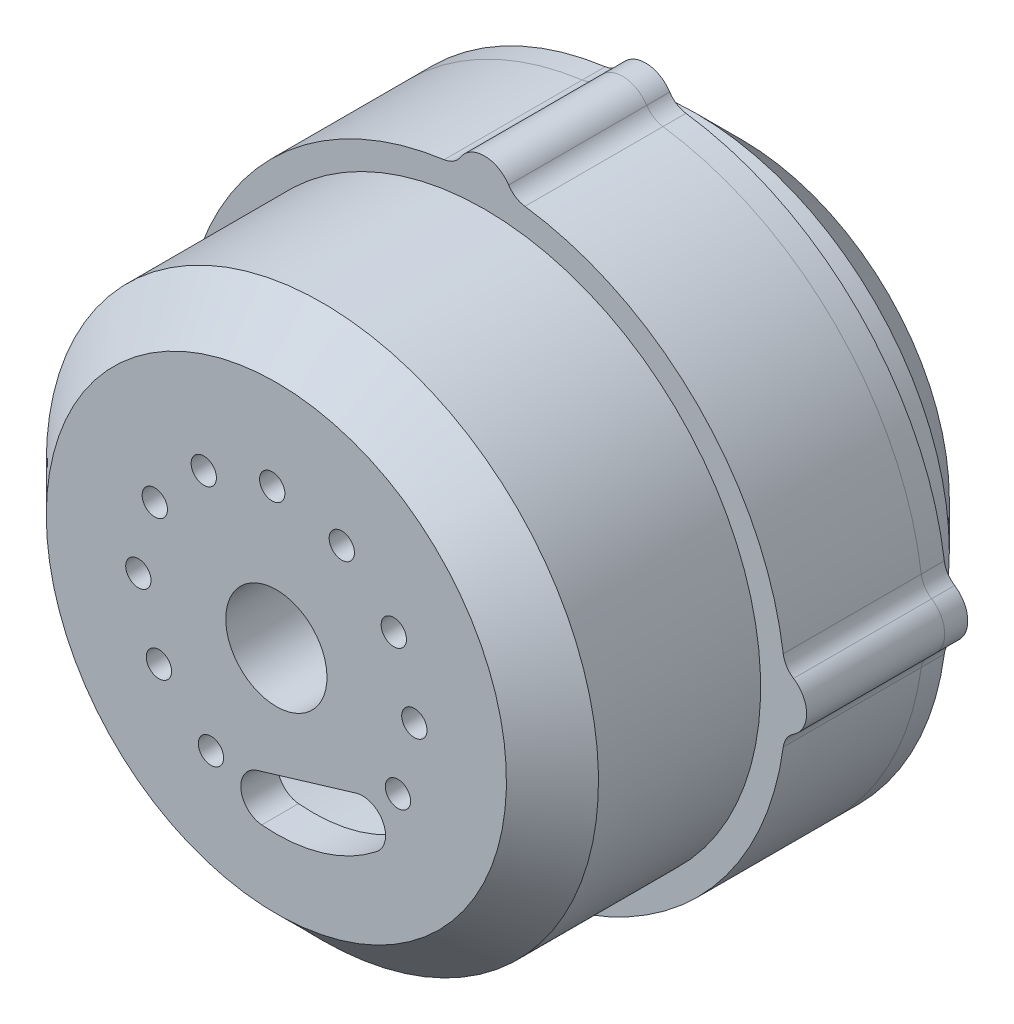
SolidWorks part; units mm, degrees
material "6061-T6 (SS)"
ref_plane "Front Plane" through (0, 0, 0) normal (0, 0, 1) x (1, 0, 0)
ref_plane "Top Plane" through (0, 0, 0) normal (0, 1, 0) x (1, 0, 0)
ref_plane "Right Plane" through (0, 0, 0) normal (1, 0, 0) x (0, 0, -1)
sketch "Sketch3" plane through (0, 0, 0) normal (1, 0, 0) x (0, 0, -1)
  line L0 (7, 57.5) -> (-6, 57.5)
  line L1 (-6, 57.5) -> (-6, 52.5)
  line L2 (-6, 57.5) -> (-6, 46.1394) construction
  line L3 (-6, 52.5) -> (-60.2341, 52.5)
  line L4 (-32.9966, 19) -> (-32.9966, 12)
  line L5 (-32.9966, 12) -> (-38.9966, 12)
  line L6 (-38.9966, 12) -> (-38.9966, 11)
  line L7 (-38.9966, 11) -> (-68.2341, 11)
  line L8 (-68.2341, -47.5) -> (-68.2341, 47.5) construction
  line L9 (-68.2341, 11) -> (-68.2341, 70)
  line L10 (-68.2341, 70) -> (7, 70)
  line L11 (7, 70) -> (7, 57.5)
  line L12 (-68.2341, 0) -> (33.0822, 0) construction
  line L14 (-38.9966, 11.7) -> (-38.9966, -11.7) construction
  line L15 (-33.2966, 12) -> (-38.6966, 12) construction
  line L16 (-32.9966, -11.7) -> (-32.9966, 11.7) construction
  line L21 (-32.9966, 19) -> (-60.2341, 19)
  line L22 (-60.2341, 19) -> (-60.2341, 52.5)
  line L23 (6, 46.1394) -> (6, 57.5) construction
  point P7 (6, 57.5)
  point P19 (7.2365, 57.5)
  point P29 (-60.0808, 52.5)
  dimension "D1" = 5
  dimension "D2" = 140
  dimension "D3" = 1
  dimension "D4" = 1
  dimension "D5" = 8
  dimension "D6" = 8
revolve "Revolve1" add sketch "Sketch3" angle 360 about L12
sketch "Sketch5" plane through (0, 0, -7) normal (0, 0, -1) x (-1, 0, 0)
  arc A16 (38.9134, -45.4201) -> (34.3133, -46.1394) centre (37.297, -50.1516) ccw
  arc A17 (38.9134, -45.4201) -> (45.4201, -38.9134) centre (40.5703, -40.5703) ccw
  arc A18 (46.1394, -34.3133) -> (45.4201, -38.9134) centre (50.1516, -37.297) ccw
  arc A19 (46.1394, -34.3133) -> (46.1394, 34.3133) centre (0, 0) ccw
  arc A20 (45.4201, 38.9134) -> (46.1394, 34.3133) centre (50.1516, 37.297) ccw
  arc A21 (45.4201, 38.9134) -> (38.9134, 45.4201) centre (40.5703, 40.5703) ccw
  arc A22 (34.3133, 46.1394) -> (38.9134, 45.4201) centre (37.297, 50.1516) ccw
  arc A23 (34.3133, 46.1394) -> (-34.3133, 46.1394) centre (0, 0) ccw
  arc A24 (-38.9134, 45.4201) -> (-34.3133, 46.1394) centre (-37.297, 50.1516) ccw
  arc A25 (-38.9134, 45.4201) -> (-45.4201, 38.9134) centre (-40.5703, 40.5703) ccw
  arc A26 (-46.1394, 34.3133) -> (-45.4201, 38.9134) centre (-50.1516, 37.297) ccw
  arc A27 (-46.1394, 34.3133) -> (-46.1394, -34.3133) centre (0, 0) ccw
  arc A28 (-45.4201, -38.9134) -> (-46.1394, -34.3133) centre (-50.1516, -37.297) ccw
  arc A29 (-45.4201, -38.9134) -> (-38.9134, -45.4201) centre (-40.5703, -40.5703) ccw
  arc A30 (-34.3133, -46.1394) -> (-38.9134, -45.4201) centre (-37.297, -50.1516) ccw
  arc A31 (-34.3133, -46.1394) -> (34.3133, -46.1394) centre (0, 0) ccw
  arc A32 (38.9134, -45.4201) -> (34.3133, -46.1394) centre (37.297, -50.1516) ccw
  arc A33 (38.9134, -45.4201) -> (45.4201, -38.9134) centre (40.5703, -40.5703) ccw
  arc A34 (46.1394, -34.3133) -> (45.4201, -38.9134) centre (50.1516, -37.297) ccw
  arc A35 (46.1394, -34.3133) -> (46.1394, 34.3133) centre (0, 0) ccw
  arc A36 (45.4201, 38.9134) -> (46.1394, 34.3133) centre (50.1516, 37.297) ccw
  arc A37 (45.4201, 38.9134) -> (38.9134, 45.4201) centre (40.5703, 40.5703) ccw
  arc A38 (34.3133, 46.1394) -> (38.9134, 45.4201) centre (37.297, 50.1516) ccw
  arc A39 (34.3133, 46.1394) -> (-34.3133, 46.1394) centre (0, 0) ccw
  arc A40 (-38.9134, 45.4201) -> (-34.3133, 46.1394) centre (-37.297, 50.1516) ccw
  arc A41 (-38.9134, 45.4201) -> (-45.4201, 38.9134) centre (-40.5703, 40.5703) ccw
  arc A42 (-46.1394, 34.3133) -> (-45.4201, 38.9134) centre (-50.1516, 37.297) ccw
  arc A43 (-46.1394, 34.3133) -> (-46.1394, -34.3133) centre (0, 0) ccw
  arc A44 (-45.4201, -38.9134) -> (-46.1394, -34.3133) centre (-50.1516, -37.297) ccw
  arc A45 (-45.4201, -38.9134) -> (-38.9134, -45.4201) centre (-40.5703, -40.5703) ccw
  arc A46 (-34.3133, -46.1394) -> (-38.9134, -45.4201) centre (-37.297, -50.1516) ccw
  arc A47 (-34.3133, -46.1394) -> (34.3133, -46.1394) centre (0, 0) ccw
  dimension "D1" = 0
extrude "Cut-Extrude2" cut sketch "Sketch5" against normal up to surface (13 mm away) up to face at (0, -57.5, 6)
sketch "Sketch6" plane through (0, 0, 6) normal (0, 0, -1) x (-1, 0, 0)
  circle A0 centre (-40.5703, 40.5703) radius 2.0193
  circle A1 centre (40.5703, 40.5703) radius 2.0193
  circle A2 centre (40.5703, -40.5703) radius 2.0193
  circle A3 centre (-40.5703, -40.5703) radius 2.0193
  dimension "D1" = 4.0386
extrude "Cut-Extrude3" cut sketch "Sketch6" against normal blind 25
sketch "Sketch4" plane through (0, 0, 68.2341) normal (0, 0, 1) x (1, 0, 0)
  line L0 (-4.1627, -25.0873) -> (17.2952, -18.6434)
  circle A0 centre (26.4181, -14.2156) radius 2.75
  circle A1 centre (29.9866, 0.8979) radius 2.75
  circle A2 centre (25.5202, 15.7709) radius 2.75
  circle A3 centre (14.2156, 26.4181) radius 2.75
  circle A4 centre (-0.8979, 29.9866) radius 2.75
  circle A5 centre (-15.7709, 25.5202) radius 2.75
  circle A6 centre (-26.4181, 14.2156) radius 2.75
  circle A7 centre (-29.9866, -0.8979) radius 2.75
  circle A8 centre (-25.5202, -15.7709) radius 2.75
  circle A9 centre (-14.2156, -26.4181) radius 2.75
  arc A10 (-14.2156, -26.4181) -> (26.4181, -14.2156) centre (0, 0) ccw construction
  arc A11 (-2.7247, -29.876) -> (18.7333, -23.4321) centre (0, 0) ccw construction
  arc A12 (-3.1788, -34.8554) -> (21.8555, -27.3375) centre (0, 0) ccw
  arc A14 (-4.1627, -25.0873) -> (-3.1788, -34.8554) centre (-2.7247, -29.876) ccw
  arc A15 (21.8555, -27.3375) -> (17.2952, -18.6434) centre (18.7333, -23.4321) ccw
  point P34 (8.6284, -28.7324)
  point P37 (21.8555, -27.3375)
  point P38 (18.7335, -23.432)
  dimension "D1" = 5.5
  dimension "D2" = 12
  dimension "D3" = 5
  dimension "D4" = 12.17
extrude "Cut-Extrude1" cut sketch "Sketch4" against normal up to next
sketch "Sketch7" plane through (0, 0, 68.2341) normal (0, 0, 1) x (1, 0, 0)
  circle A2 centre (0, 0) radius 60
  dimension "D1" = 120
extrude "Cut-Extrude4" cut sketch "Sketch7" against normal offset from surface (45.2341 mm away) 30 flip side to cut up to face at (0, 0, -7)
sketch "Sketch8" plane through (0, 0, -7) normal (0, 0, -1) x (-1, 0, 0)
  line L0 (-70, 0) -> (-57.5, 0) construction
  circle A0 centre (-63.75, 0) radius 2.4892
  circle A1 centre (0, 0) radius 70 construction
  arc A2 (-46.1394, 34.3133) -> (-46.1394, -34.3133) centre (0, 0) ccw construction
  circle A3 centre (0, 63.75) radius 2.4892
  circle A4 centre (63.75, 0) radius 2.4892
  circle A5 centre (0, -63.75) radius 2.4892
  arc A8 (-67.1471, 5.2462) -> (-67.1471, -5.2462) centre (-63.75, 0) ccw
  arc A9 (5.2462, 67.1471) -> (-5.2462, 67.1471) centre (0, 63.75) ccw
  arc A10 (67.1471, -5.2462) -> (67.1471, 5.2462) centre (63.75, 0) ccw
  arc A11 (-5.2462, -67.1471) -> (5.2462, -67.1471) centre (0, -63.75) ccw
  arc A12 (-64.9098, -8.7734) -> (-8.7734, -64.9098) centre (0, 0) ccw
  arc A13 (-8.7734, 64.9098) -> (-64.9098, 8.7734) centre (0, 0) ccw
  arc A14 (64.9098, 8.7734) -> (8.7734, 64.9098) centre (0, 0) ccw
  arc A15 (8.7734, -64.9098) -> (64.9098, -8.7734) centre (0, 0) ccw
  arc A16 (-5.2462, -67.1471) -> (-8.7734, -64.9098) centre (-9.4431, -69.8647) ccw
  arc A17 (5.2462, -67.1471) -> (8.7734, -64.9098) centre (9.4431, -69.8647) cw
  arc A18 (67.1471, -5.2462) -> (64.9098, -8.7734) centre (69.8647, -9.4431) ccw
  arc A19 (67.1471, 5.2462) -> (64.9098, 8.7734) centre (69.8647, 9.4431) cw
  arc A20 (5.2462, 67.1471) -> (8.7734, 64.9098) centre (9.4431, 69.8647) ccw
  arc A21 (-5.2462, 67.1471) -> (-8.7734, 64.9098) centre (-9.4431, 69.8647) cw
  arc A22 (-64.9098, -8.7734) -> (-67.1471, -5.2462) centre (-69.8647, -9.4431) ccw
  arc A23 (-67.1471, 5.2462) -> (-64.9098, 8.7734) centre (-69.8647, 9.4431) ccw
  circle A24 centre (0, 0) radius 70
  point P18 (0, 0)
  point P32 (0, 0)
  point P33 (6.0752, -65.2176)
  point P38 (65.2176, 6.0752)
  point P43 (-6.0752, 65.2176)
  point P48 (0, 0)
  circle M37 centre (0, 0) radius 70
  dimension "D1" = 4.9784
  dimension "D3" = 65.5
  dimension "D4" = 4
  dimension "D5" = 5
  dimension "D2" = 4
extrude "Cut-Extrude5" cut sketch "Sketch8" against normal through all contours A8 A23 A13 A21 A9 M37 | A9 A20 A14 A19 A10 M37 | A10 A18 A15 A17 A11 M37 | A12 A22 A8 A11 A16 M37 region at (69.3276, 3.0332, -7) region at (69.3276, -3.0332, -7) region at (-48.7975, 48.7975, -7) region at (-3.0332, -69.3276, -7)
chamfer "Chamfer1" distance 10 angle 45 1 edges at (60, 0, 68.2341)
extrude "Cut-Extrude6" cut sketch "Sketch8<3>" against normal blind 25 contours A0 | A3 | A4 | A5
sketch "Sketch8<3>" plane through (0, 0, -7) normal (0, 0, -1) x (-1, 0, 0) same geometry as "Sketch8"
sketch "Sketch9" plane through (0, 0, -7) normal (0, 0, -1) x (-1, 0, 0)
  circle A0 centre (0, -63.75) radius 2.4892 construction
  circle A1 centre (63.75, 0) radius 2.4892 construction
  circle A2 centre (0, 63.75) radius 2.4892 construction
  circle A3 centre (-63.75, 0) radius 2.4892 construction
  circle A4 centre (0, -63.75) radius 2.4892
  circle A5 centre (63.75, 0) radius 2.4892
  circle A6 centre (0, 63.75) radius 2.4892
  circle A7 centre (-63.75, 0) radius 2.4892
  circle A8 centre (0, 0) radius 50
  arc A16 (-5.2462, -67.1471) -> (-8.7734, -64.9098) centre (-9.4431, -69.8647) ccw
  arc A17 (-5.2462, -67.1471) -> (5.2462, -67.1471) centre (0, -63.75) ccw
  arc A18 (8.7734, -64.9098) -> (5.2462, -67.1471) centre (9.4431, -69.8647) ccw
  arc A19 (8.7734, -64.9098) -> (64.9098, -8.7734) centre (0, 0) ccw
  arc A20 (67.1471, -5.2462) -> (64.9098, -8.7734) centre (69.8647, -9.4431) ccw
  arc A21 (67.1471, -5.2462) -> (67.1471, 5.2462) centre (63.75, 0) ccw
  arc A22 (64.9098, 8.7734) -> (67.1471, 5.2462) centre (69.8647, 9.4431) ccw
  arc A23 (64.9098, 8.7734) -> (8.7734, 64.9098) centre (0, 0) ccw
  arc A24 (5.2462, 67.1471) -> (8.7734, 64.9098) centre (9.4431, 69.8647) ccw
  arc A25 (5.2462, 67.1471) -> (-5.2462, 67.1471) centre (0, 63.75) ccw
  arc A26 (-8.7734, 64.9098) -> (-5.2462, 67.1471) centre (-9.4431, 69.8647) ccw
  arc A27 (-8.7734, 64.9098) -> (-64.9098, 8.7734) centre (0, 0) ccw
  arc A28 (-67.1471, 5.2462) -> (-64.9098, 8.7734) centre (-69.8647, 9.4431) ccw
  arc A29 (-67.1471, 5.2462) -> (-67.1471, -5.2462) centre (-63.75, 0) ccw
  arc A30 (-64.9098, -8.7734) -> (-67.1471, -5.2462) centre (-69.8647, -9.4431) ccw
  arc A31 (-64.9098, -8.7734) -> (-8.7734, -64.9098) centre (0, 0) ccw
  arc A32 (-5.2462, -67.1471) -> (-8.7734, -64.9098) centre (-9.4431, -69.8647) ccw
  arc A33 (-5.2462, -67.1471) -> (5.2462, -67.1471) centre (0, -63.75) ccw
  arc A34 (8.7734, -64.9098) -> (5.2462, -67.1471) centre (9.4431, -69.8647) ccw
  arc A35 (8.7734, -64.9098) -> (64.9098, -8.7734) centre (0, 0) ccw
  arc A36 (67.1471, -5.2462) -> (64.9098, -8.7734) centre (69.8647, -9.4431) ccw
  arc A37 (67.1471, -5.2462) -> (67.1471, 5.2462) centre (63.75, 0) ccw
  arc A38 (64.9098, 8.7734) -> (67.1471, 5.2462) centre (69.8647, 9.4431) ccw
  arc A39 (64.9098, 8.7734) -> (8.7734, 64.9098) centre (0, 0) ccw
  arc A40 (5.2462, 67.1471) -> (8.7734, 64.9098) centre (9.4431, 69.8647) ccw
  arc A41 (5.2462, 67.1471) -> (-5.2462, 67.1471) centre (0, 63.75) ccw
  arc A42 (-8.7734, 64.9098) -> (-5.2462, 67.1471) centre (-9.4431, 69.8647) ccw
  arc A43 (-8.7734, 64.9098) -> (-64.9098, 8.7734) centre (0, 0) ccw
  arc A44 (-67.1471, 5.2462) -> (-64.9098, 8.7734) centre (-69.8647, 9.4431) ccw
  arc A45 (-67.1471, 5.2462) -> (-67.1471, -5.2462) centre (-63.75, 0) ccw
  arc A46 (-64.9098, -8.7734) -> (-67.1471, -5.2462) centre (-69.8647, -9.4431) ccw
  arc A47 (-64.9098, -8.7734) -> (-8.7734, -64.9098) centre (0, 0) ccw
  dimension "D2" = 100
  dimension "D1" = 0
extrude "Boss-Extrude3" add sketch "Sketch9" along normal blind 5 separate body
sketch "Sketch10" plane through (0, 0, 0) normal (1, 0, 0) x (0, 0, -1)
  line L0 (12, 70) -> (33, 70)
  line L1 (33, 70) -> (33, 12)
  line L2 (33, 12) -> (27, 12)
  line L3 (27, 12) -> (27, 11)
  line L4 (27, 11) -> (17, 11)
  line L5 (17, 11) -> (17, 12)
  line L6 (17, 12) -> (12, 12)
  line L7 (12, 8.7734) -> (12, 64.9098) construction
  line L8 (12, 12) -> (12, 70)
  line L9 (32.7, 12) -> (27.3, 12) construction
  line L10 (27, 11.7) -> (27, -11.7) construction
  line L11 (17, -11.7) -> (17, 11.7) construction
  line L12 (33, -11.7) -> (33, 11.7) construction
  line L13 (0, 0) -> (-23, 0) construction
  line L14 (-23, 5.2462) -> (-23, -5.2462) construction
  dimension "D1" = 1
revolve "Revolve2" add sketch "Sketch10" angle 360 about L13
sketch "Sketch11" plane through (0, 0, -12) normal (0, 0, 1) x (1, 0, 0)
  circle A0 centre (0, 0) radius 55
  dimension "D1" = 110
extrude "Cut-Extrude7" cut sketch "Sketch11" against normal through all flip side to cut
chamfer "Chamfer2" distance 10 angle 45 1 edges at (55, 0, -33)
sketch "Sketch13" plane through (0, 0, -12) normal (0, 0, 1) x (1, 0, 0)
  circle A0 centre (0, 0) radius 25
  circle A1 centre (0, 0) radius 50 construction
  circle A2 centre (0, 0) radius 50
  dimension "D1" = 50
extrude "Cut-Extrude9" cut sketch "Sketch13" against normal blind 10
chamfer "Chamfer3" distance 5 angle 45 1 edges at (25, 0, -12)
